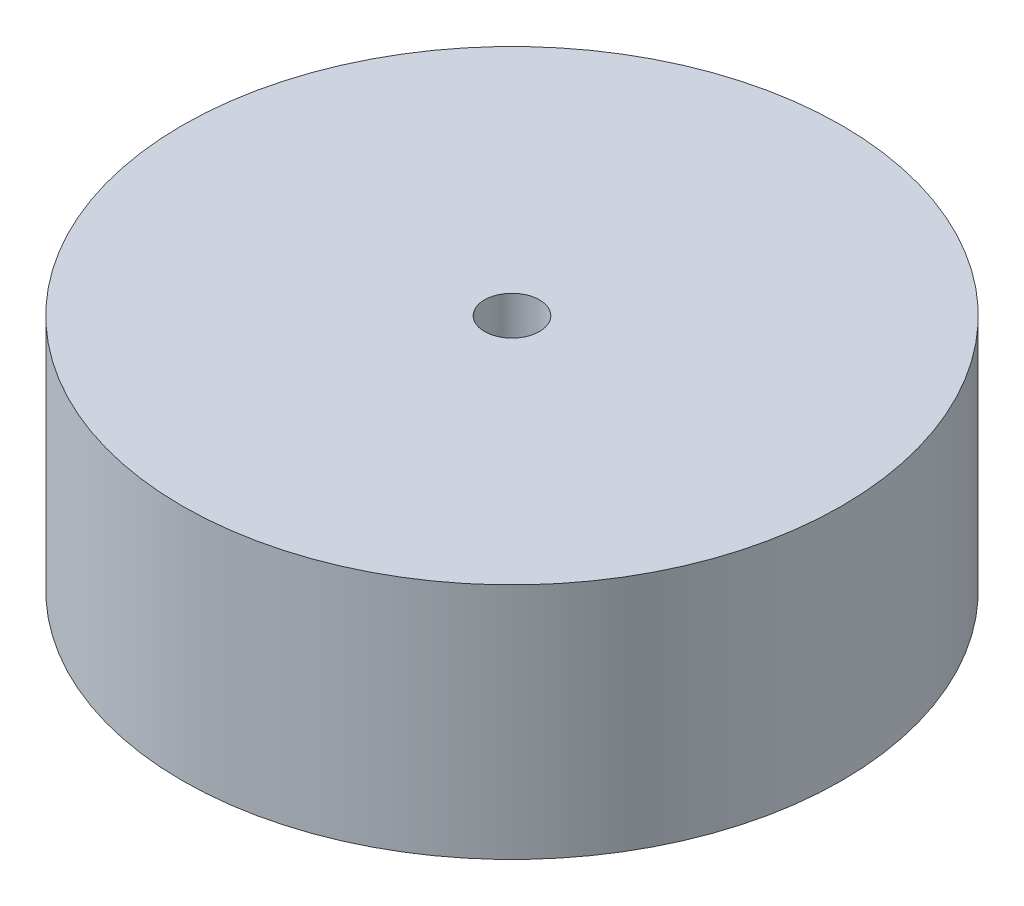
SolidWorks part; units mm, degrees
ref_plane "Front Plane" through (0, 0, 0) normal (0, 0, 1) x (1, 0, 0)
ref_plane "Top Plane" through (0, 0, 0) normal (0, 1, 0) x (1, 0, 0)
ref_plane "Right Plane" through (0, 0, 0) normal (1, 0, 0) x (0, 0, -1)
sketch "Sketch1" plane through (0, 0, 0) normal (0, 1, 0) x (1, 0, 0)
  circle A0 centre (0, 0) radius 15
  dimension "D1" = 30
extrude "Boss-Extrude2" add sketch "Sketch1" along normal blind 10.82 contours A0
sketch "Sketch2" plane through (0, 10.82, 0) normal (0, 1, 0) x (1, 0, 0)
  circle A0 centre (0, 0) radius 1.25
  dimension "D1" = 2.5
extrude "Cut-Extrude1" cut sketch "Sketch2" against normal blind 7.65
